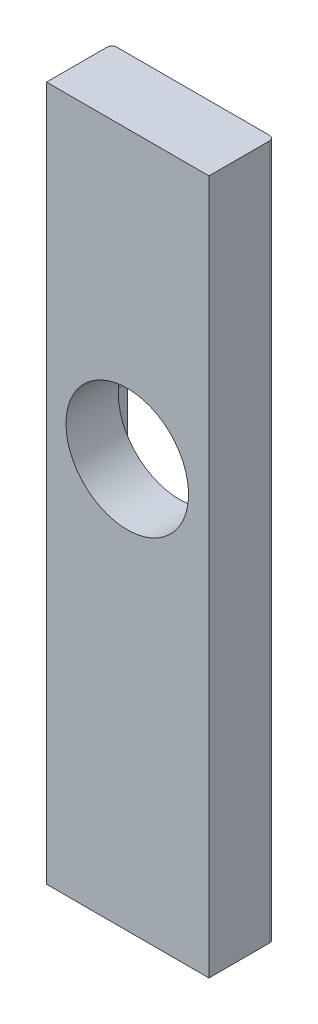
SolidWorks part; units mm, degrees
ref_plane "Front Plane" through (0, 0, 0) normal (0, 0, 1) x (1, 0, 0)
ref_plane "Top Plane" through (0, 0, 0) normal (0, 1, 0) x (1, 0, 0)
ref_plane "Right Plane" through (0, 0, 0) normal (1, 0, 0) x (0, 0, -1)
sketch "Sketch1" plane through (0, 0, 0) normal (0, 0, 1) x (1, 0, 0)
  line L0 (-6.2738, 53.975) -> (-6.2738, 0)
  line L1 (-6.2738, 53.975) -> (6.35, 53.975)
  line L2 (-6.2738, 0) -> (6.35, 0)
  line L3 (6.35, 53.975) -> (6.35, 0)
  line L4 (-6.2738, 53.975) -> (6.35, 0) construction
  line L5 (-6.2738, 0) -> (6.35, 53.975) construction
  point P1 (0.0381, 26.9875)
  dimension "flue_plug_width" = 12.6238
  dimension "flue_plug_length" = 53.975
extrude "blank" add sketch "Sketch1" along normal blind 5.08
sketch "Sketch2" plane through (0, 0, 0) normal (0, 0, 1) x (1, 0, 0)
  line L0 (0, -31.75) -> (0, 31.75) construction
  line L1 (-5.08, -31.75) -> (-5.08, 31.75)
  line L2 (5.08, -31.75) -> (5.08, 31.75)
  line L4 (6.35, 53.975) -> (-6.2738, 53.975) construction
  arc A0 (-5.08, -31.75) -> (5.08, -31.75) centre (0, -31.75) ccw
  arc A1 (5.08, 31.75) -> (-5.08, 31.75) centre (0, 31.75) ccw
  point P2 (0, 0)
  dimension "slot_radius" = 5.08
  dimension "slot_location" = 22.225
extrude "slot" cut sketch "Sketch2" along normal blind 1.016
sketch "Sketch3" plane through (0, 0, 1.016) normal (0, 0, -1) x (-1, 0, 0)
  circle A0 centre (0, 31.75) radius 4.7625
  arc A1 (5.08, 31.75) -> (-5.08, 31.75) centre (0, 31.75) ccw construction
  dimension "airway_passage" = 9.525
extrude "through_hole" cut sketch "Sketch3" against normal through all
fillet "Fillet1" radius 0.381 2 edges at (-6.2738, 26.9875, 0) (6.35, 26.9875, 0)
